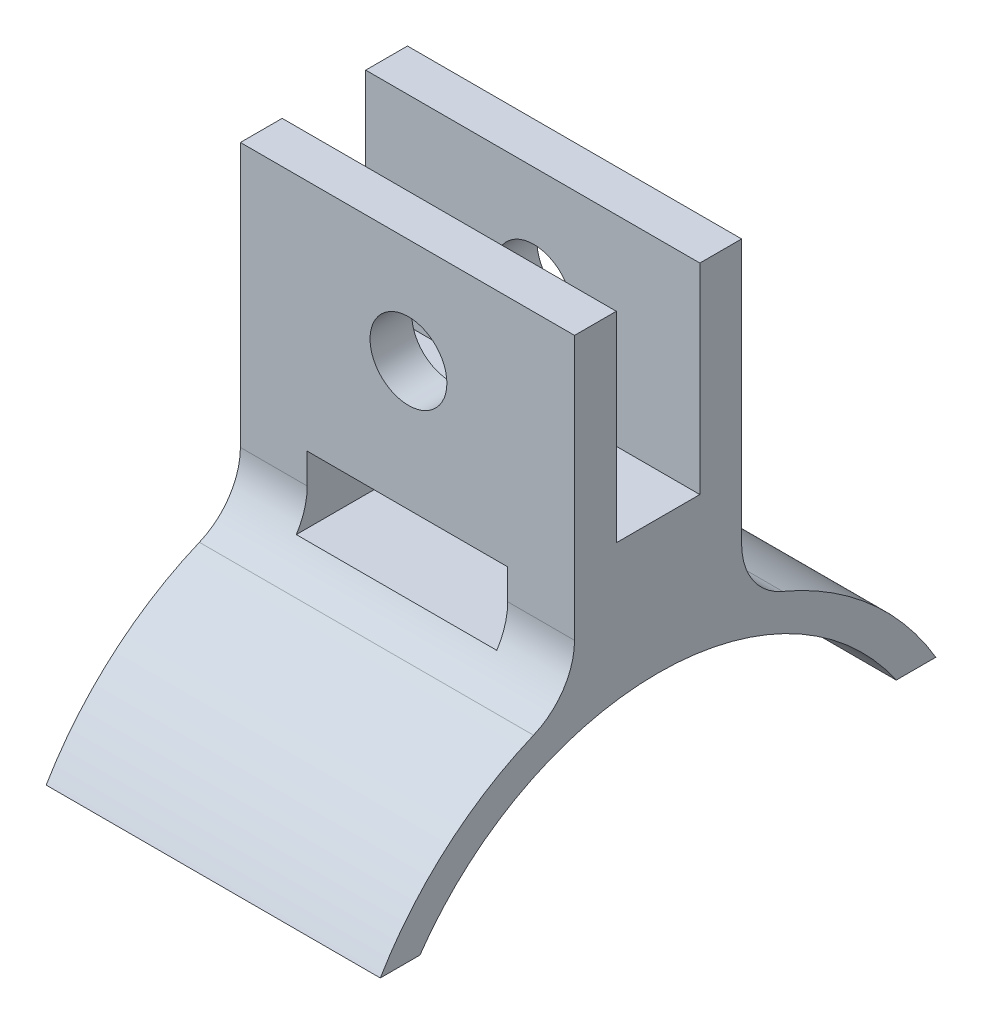
SolidWorks part; units mm, degrees
ref_plane "Front Plane" through (0, 0, 0) normal (0, 0, 1) x (1, 0, 0)
ref_plane "Top Plane" through (0, 0, 0) normal (0, 1, 0) x (1, 0, 0)
ref_plane "Right Plane" through (0, 0, 0) normal (1, 0, 0) x (0, 0, -1)
sketch "Sketch1" plane through (0, 0, 0) normal (1, 0, 0) x (0, 0, -1)
  circle A0 centre (0, 0) radius 10.9855
  circle A1 centre (0, 0) radius 12.2555
  dimension "D1" = 21.971
  dimension "D2" = 1.27
extrude "Boss-Extrude1" add sketch "Sketch1" along normal blind 27.94
sketch "Sketch2" plane through (0, 0, 0) normal (0, 1, 0) x (1, 0, 0)
  line L0 (0, 12.2555) -> (0, -12.2555) construction
  line L1 (0, 11.9205) -> (6.35, 11.9205)
  line L2 (0, 11.9205) -> (0, -11.9205)
  line L3 (0, -11.9205) -> (6.35, -11.9205)
  line L4 (6.35, 11.9205) -> (6.35, -11.9205)
  line L5 (27.94, 12.2555) -> (0, 12.2555) construction
  line L6 (0, -12.2555) -> (27.94, -12.2555) construction
  line L8 (27.94, 12.2555) -> (20.066, 12.2555)
  line L9 (27.94, 12.2555) -> (27.94, 11.3205)
  line L10 (27.94, 11.3205) -> (20.066, 11.3205)
  line L11 (20.066, 12.2555) -> (20.066, 11.3205)
  line L12 (27.94, -12.2555) -> (20.066, -12.2555)
  line L13 (27.94, -12.2555) -> (27.94, -11.3205)
  line L14 (27.94, -11.3205) -> (20.066, -11.3205)
  line L15 (20.066, -12.2555) -> (20.066, -11.3205)
  dimension "D1" = 0.335
  dimension "D2" = 6.35
  dimension "D3" = 0.335
  dimension "D4" = 0.935
  dimension "D5" = 7.874
extrude "Cut-Extrude1" cut sketch "Sketch2" against normal through all and the other way through all
sketch "Sketch4" plane through (0, 0, 0) normal (0, 0, 1) x (1, 0, 0)
  line L0 (0, 0) -> (27.94, 0) construction
  line L1 (27.94, -4.6951) -> (27.94, 4.6951) construction
  circle A0 centre (25.019, 0) radius 1.6
  circle A1 centre (3.175, 0) radius 1.6
  dimension "D1" = 3.2
  dimension "D2" = 3.175
  dimension "D3" = 21.844
extrude "Cut-Extrude2" cut sketch "Sketch4" against normal through all and the other way through all contours A1
sketch "Sketch8" plane through (0, 0, -11.9205) normal (0, 0, 1) x (1, 0, 0)
  line L41 (0, -2.8459) -> (0, 2.8459) construction
  line L42 (0, 2.8459) -> (6.35, 2.8459) construction
  line L43 (0, 0) -> (6.35, 0) construction
  line L44 (6.35, -2.8459) -> (6.35, 2.8459) construction
  line L45 (2.8459, -2.8459) -> (0, -2.8459)
  line L46 (0, -2.8459) -> (0, 2.8459)
  line L47 (0, 2.8459) -> (2.8459, 2.8459)
  arc A0 (2.8459, -2.8459) -> (2.8459, 2.8459) centre (2.8459, 0) cw
  line M3 (6.35, 2.8459) -> (0, 2.8459)
  line M4 (0, 2.8459) -> (0, -2.8459)
  line M5 (0, -2.8459) -> (6.35, -2.8459)
extrude "Cut-Extrude6" cut sketch "Sketch8" against normal through all and the other way through all contours A0 M4 M3 | A0 L46 M5 region at (0.6357, 2.2102, -11.9205) region at (0.6357, -2.2102, -11.9205)
ref_plane "Plane1" through (0, 12.2555, 0) normal (0, 1, 0) x (1, 0, 0)
sketch "Sketch9" plane through (0, 12.2555, 0) normal (0, 1, 0) x (1, 0, 0)
  line L0 (6.35, -3.175) -> (6.35, 3.175)
  line L1 (6.35, -3.175) -> (27.94, -3.175)
  line L2 (6.35, 3.175) -> (27.94, 3.175)
  line L3 (27.94, -3.175) -> (27.94, 3.175)
  line L4 (6.35, 11.9205) -> (6.35, -11.9205) construction
  line L5 (27.94, -11.3205) -> (27.94, 11.3205) construction
  point P6 (6.35, 0)
  point P7 (6.35, 0)
  dimension "D2" = 6.35
extrude "Boss-Extrude2" add sketch "Sketch9" along normal blind 11.43 and the other way up to next (1.27 mm away)
sketch "Sketch11" plane through (0, 0, 3.175) normal (0, 0, 1) x (1, 0, 0)
  line L0 (6.35, 23.6855) -> (27.94, 23.6855) construction
  circle A0 centre (17.145, 19.685) radius 1.4605
  point P2 (17.145, 21.1455)
  point P5 (17.145, 23.6855)
  point P8 (17.145, 18.2245)
  point P9 (18.6055, 19.685)
  dimension "D1" = 2.921
  dimension "D2" = 2.54
extrude "Cut-Extrude8" cut sketch "Sketch11" against normal through all
sketch "Sketch10" plane through (6.35, 0, 0) normal (-1, 0, 0) x (0, 0, 1)
  line L0 (-1.5875, 23.6855) -> (1.5875, 23.6855)
  line L1 (-1.5875, 23.6855) -> (-1.5875, 16.0655)
  line L2 (1.5875, 23.6855) -> (1.5875, 16.0655)
  line L3 (-1.5875, 16.0655) -> (1.5875, 16.0655)
  line L4 (-3.175, 23.6855) -> (3.175, 23.6855) construction
  point P6 (0, 23.6855)
  dimension "D1" = 3.175
  dimension "D2" = 7.62
extrude "Cut-Extrude7" cut sketch "Sketch10" against normal through all
sketch "Sketch12" plane through (27.94, 0, 0) normal (1, 0, 0) x (0, 0, -1)
  line L0 (-11.9205, -2.8459) -> (11.9205, -2.8459)
  line L1 (-11.9205, -2.8459) -> (-11.9205, -12.2555)
  line L2 (11.9205, -2.8459) -> (11.9205, -12.2555)
  line L3 (-11.9205, -12.2555) -> (11.9205, -12.2555)
  line L4 (-10.9855, 0) -> (-10.9855, -2.8459)
  line L5 (-10.9855, 0) -> (10.9855, 0)
  line L6 (10.9855, 0) -> (10.9855, -2.8459)
  arc A0 (-11.9205, -2.8459) -> (11.9205, -2.8459) centre (0, 0) ccw construction
  arc A2 (-11.3205, -4.6951) -> (11.3205, -4.6951) centre (0, 0) ccw construction
  circle A3 centre (0, 0) radius 10.9855 construction
  arc M8 (-11.3205, -4.6951) -> (11.3205, -4.6951) centre (0, 0) ccw
  circle M13 centre (0, 0) radius 10.9855
extrude "Cut-Extrude9" cut sketch "Sketch12" against normal through all contours L5 L0 M13 | L4 L0 M13 | L6 L0 M13 | L0 M8 M13 | L3 L2 M8 | L0 M13 | L1 L3 M8 region at (27.94, -3.1022, 11.453) region at (27.94, -2.1369, 10.8733) region at (27.94, -1.4148, 0) region at (27.94, -6.234, 0) region at (27.94, -2.1369, -10.8733)
sketch "Sketch13" plane through (0, 0, 11.9205) normal (0, 0, -1) x (-1, 0, 0)
  line L1 (-6.35, -2.8459) -> (-9.35, -2.8459)
  line L2 (-6.35, -2.8459) -> (-6.35, 2.8459)
  line L3 (-6.35, -2.8459) -> (-2.8459, -2.8459)
  line L4 (-2.8459, 2.8459) -> (-6.35, 2.8459)
  line L5 (-6.35, 2.8459) -> (-6.35, -2.8459)
  line L6 (-6.35, -2.8459) -> (-2.8459, -2.8459)
  line L7 (-2.8459, 2.8459) -> (-6.35, 2.8459)
  line L8 (-6.35, 2.8459) -> (-6.35, -2.8459)
  line L9 (-6.35, 2.8459) -> (-9.35, 2.8459)
  line L10 (-9.35, -2.8459) -> (-9.35, 2.8459)
  circle A0 centre (-3.175, 0) radius 1.6 construction
  arc A1 (-2.8459, -2.8459) -> (-2.8459, 2.8459) centre (-2.8459, 0) ccw
  arc A2 (-2.8459, -2.8459) -> (-2.8459, 2.8459) centre (-2.8459, 0) ccw
  circle A3 centre (-3.175, 0) radius 1.6
  circle M5 centre (-3.175, 0) radius 1.6
  line M6 (-6.35, -2.8459) -> (-2.8459, -2.8459)
  arc M7 (-2.8459, -2.8459) -> (-2.8459, 2.8459) centre (-2.8459, 0) ccw
  line M8 (-2.8459, 2.8459) -> (-6.35, 2.8459)
  line M9 (-6.35, 2.8459) -> (-6.35, -2.8459)
  dimension "D2" = 3
  dimension "D1" = 0
extrude "Boss-Extrude3" add sketch "Sketch13" against normal blind 1 contours M9 M6 M7 M8 M5 | L10 L1 L9 M9 region at (7.85, 0, 11.9205) region at (6.2647, 0, 11.9205)
fillet "Fillet3" radius 2.54 2 edges at (9.35, 0, 12.2555) (7.85, 2.8459, 11.9205)
mirror "Mirror1" about plane through (0, 0, 0) normal (0, 0, 1) of "Fillet3", "Boss-Extrude3"
sketch "Sketch15" plane through (6.35, 0, 0) normal (-1, 0, 0) x (0, 0, 1)
  arc A0 (11.4703, 4.3161) -> (12.9205, 2.8459) centre (13.8476, 5.2106) ccw construction
  arc A1 (11.4703, 4.3161) -> (12.9205, 2.8459) centre (13.8476, 5.2106) ccw
sketch "Sketch16" plane through (0, 0, -11.3205) normal (0, 0, -1) x (-1, 0, 0)
  line L0 (0, 0) -> (-27.94, 0) construction
  circle A0 centre (-25.019, 0) radius 1.2875
  dimension "D1" = 2.575
  dimension "D2" = 2.921
extrude "Boss-Extrude4" add sketch "Sketch16" along normal blind 2.197
mirror "Mirror2" about plane through (0, 0, 0) normal (0, 0, 1) of "Boss-Extrude4"
fillet "Fillet6" radius 2.54 2 edges at (17.145, 11.8371, -3.175) (17.145, 11.8371, 3.175)
sketch "Sketch19" plane through (27.94, 0, 0) normal (1, 0, 0) x (0, 0, -1)
  line L0 (-10.9855, -2.8459) -> (-10.4205, -2.8459)
  line L1 (-10.4205, -2.8459) -> (-10.4205, 3.4777)
  line L2 (-10.9855, 0) -> (-10.9855, -2.8459) construction
  line L3 (-10.9855, 0) -> (-10.9855, -2.8459)
  arc A0 (10.9855, 0) -> (-10.9855, 0) centre (0, 0) ccw construction
  arc A1 (10.9855, 0) -> (-10.9855, 0) centre (0, 0) ccw
  line M8 (-10.9855, -2.8459) -> (-10.9855, 0)
  arc M9 (-10.9855, 0) -> (10.9855, 0) centre (0, 0) cw
  dimension "D1" = 1.5
extrude "Boss-Extrude6" add sketch "Sketch19" against normal up to surface (21.59 mm away) contours L0 L1 M9 M8 region at (27.94, -0.193, 10.6778) up to face at (6.35, 8.9548, 0)
mirror "Mirror3" about plane through (0, 0, 0) normal (0, 0, 1) of "Boss-Extrude6"
fillet "Fillet8" radius 5.08 2 edges at (17.145, 3.4777, -10.4205) (17.145, 3.4777, 10.4205)
sketch "Sketch27" plane through (0, 0, -3.175) normal (0, 0, -1) x (-1, 0, 0)
  line L0 (-27.8649, 16.0655) -> (-6.35, 16.0655) construction
  line L1 (-27.8649, 16.0655) -> (-6.35, 16.0655)
  line L3 (-20.9174, 14.7955) -> (-13.2974, 14.7955)
  line L4 (-20.9174, 14.7955) -> (-20.9174, 12.2555)
  line L5 (-20.9174, 12.2555) -> (-13.2974, 12.2555)
  line L6 (-13.2974, 14.7955) -> (-13.2974, 12.2555)
  line L7 (-20.9174, 14.7955) -> (-13.2974, 12.2555) construction
  line L8 (-20.9174, 12.2555) -> (-13.2974, 14.7955) construction
  point P2 (-17.1074, 13.5255)
  point P7 (-17.1074, 16.0655)
  line M5 (-27.8649, 13.6472) -> (-6.35, 13.6472)
  dimension "D1" = 7.62
  dimension "D2" = 2.54
  dimension "D3" = 1.27
extrude "Cut-Extrude12" cut sketch "Sketch27" against normal through all and the other way through all contours L6 L3 L4 M5 | L6 L4 L5 M5 region at (17.1074, 14.2213, -3.175) region at (17.1074, 12.9513, -3.175)
sketch "Sketch28" plane through (0, 0, 3.175) normal (0, 0, 1) x (1, 0, 0)
  line L0 (6.35, 23.6855) -> (27.94, 23.6855) construction
  line L1 (10.7574, 23.6855) -> (0, 23.6855)
  line L2 (10.7574, 23.6855) -> (10.7574, -2.8459)
  line L3 (10.7574, -2.8459) -> (0, -2.8459)
  line L4 (0, 23.6855) -> (0, -2.8459)
  line L5 (9.35, -2.8459) -> (2.8459, -2.8459) construction
  line L6 (23.4574, 23.6855) -> (27.94, 23.6855)
  line L7 (23.4574, 23.6855) -> (23.4574, -2.8459)
  line L8 (23.4574, -2.8459) -> (27.94, -2.8459)
  line L9 (27.94, 23.6855) -> (27.94, -2.8459)
  line L10 (13.2974, 12.2555) -> (13.2974, 13.6472) construction
  line L11 (20.9174, 13.6472) -> (20.9174, 12.2555) construction
  line L12 (27.94, 11.3043) -> (6.35, 11.3043) construction
  line L13 (10.7574, 6.2243) -> (23.4574, 6.2243)
  line L14 (10.7574, 6.2243) -> (10.7574, -2.8459)
  line L15 (10.7574, -2.8459) -> (23.4574, -2.8459)
  line L16 (23.4574, 6.2243) -> (23.4574, -2.8459)
  arc A0 (2.8459, 2.8459) -> (2.8459, -2.8459) centre (2.8459, 0) ccw construction
  line M5 (20.9174, 13.6472) -> (27.94, 13.6472)
  line M6 (27.94, 13.6472) -> (27.94, 23.6855)
  line M7 (27.94, 23.6855) -> (6.35, 23.6855)
  line M8 (6.35, 23.6855) -> (6.35, 13.6472)
  line M9 (6.35, 13.6472) -> (13.2974, 13.6472)
  dimension "D1" = 2.54
  dimension "D2" = 2.54
  dimension "D3" = 5.08
extrude "Cut-Extrude13" cut sketch "Sketch28" against normal through all and the other way through all contours L2 M7 M8 M9 | L1 L4 L3 L2 M9 M8 | L2 L15 L7 L13 | L7 M7 M5 M6 | L9 L7 L8 M5 region at (8.5537, 18.6663, 3.175) region at (4.7962, 8.9069, 3.175) region at (25.6987, 18.6663, 3.175) region at (17.1074, 1.6892, 3.175) region at (25.6987, 5.4007, 3.175)
